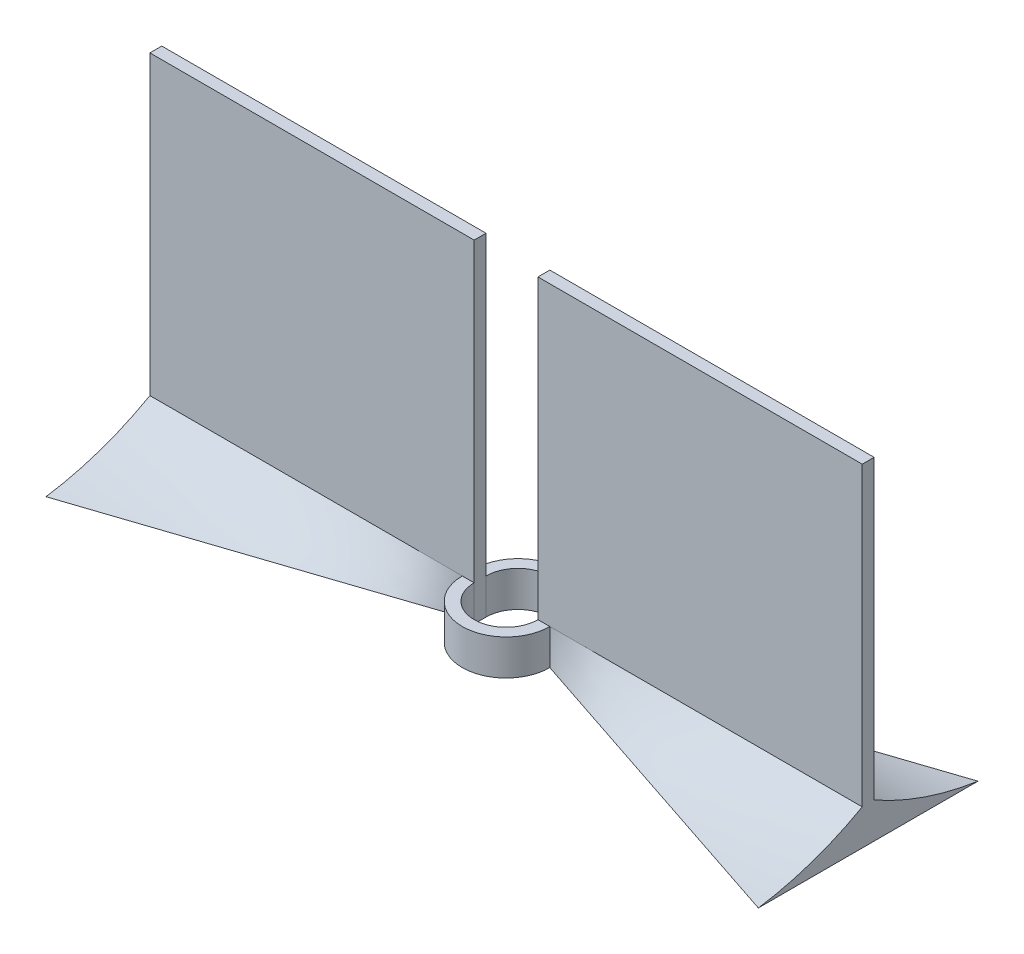
SolidWorks part; units mm, degrees
ref_plane "Front Plane" through (0, 0, 0) normal (0, 0, 1) x (1, 0, 0)
ref_plane "Top Plane" through (0, 0, 0) normal (0, 1, 0) x (1, 0, 0)
ref_plane "Right Plane" through (0, 0, 0) normal (1, 0, 0) x (0, 0, -1)
ref_plane "Plane1" through (10.75, 0, 0) normal (1, 0, 0) x (0, 0, -1)
ref_plane "Plane2" through (120, 0, 0) normal (1, 0, 0) x (0, 0, -1)
sketch "Sketch1" plane through (10.75, 0, 0) normal (1, 0, 0) x (0, 0, -1)
  line L0 (0, 0) -> (0, 12)
  line L1 (0, 55) -> (0, -55) construction
  line L2 (0, 12) -> (0, 112)
  line L3 (0, 112) -> (2, 112)
  line L4 (0, 112) -> (-2, 112)
  line L6 (2, 112) -> (-2, 112)
  line L7 (2, 112) -> (2, 12)
  line L8 (2, 12) -> (-2, 12)
  line L9 (-2, 112) -> (-2, 12)
  line L10 (2, 12) -> (-2, 12)
  line L11 (2, 12) -> (2, 0)
  line L12 (2, 0) -> (-2, 0)
  line L13 (-2, 12) -> (-2, 0)
  dimension "D1" = 100
  dimension "D2" = 4
  dimension "D3" = 12
extrude "Boss-Extrude1" add sketch "Sketch1" along normal blind 109.25 contours L7 L6 L9 L8
sketch "Sketch5" plane through (120, 0, 0) normal (1, 0, 0) x (0, 0, -1)
  line L1 (-2, 12) -> (2, 12)
  line L6 (-37, 0) -> (37, 0)
  spline S0 degree 2 poles (-2, 12) (-18.4033, 2.78) (-37, 0) knots 0 0 0 1 1 1
  spline S1 degree 2 poles (2, 12) (18.4033, 2.78) (37, 0) knots 0 0 0 1 1 1
  dimension "D1" = 74
  dimension "D2" = 4
sketch "Sketch6" plane through (10.75, 0, 0) normal (-1, 0, 0) x (0, 0, 1)
  line L3 (-2, 12) -> (2, 12)
  line L4 (-2, 12) -> (-2, 0)
  line L5 (-2, 0) -> (2, 0)
  line L6 (2, 12) -> (2, 0)
  dimension "D1" = 12
ref_plane "Plane3" through (14.75, 0, 0) normal (1, 0, 0) x (0, 0, -1)
sketch "Sketch7" plane through (14.75, 0, 0) normal (1, 0, 0) x (0, 0, -1)
  line L1 (-2, 12) -> (2, 12)
  line L2 (-2, 12) -> (-2, 0)
  line L3 (-2, 0) -> (2, 0)
  line L4 (2, 12) -> (2, 0)
  point P6 (0, 0)
extrude "Boss-Extrude2" add sketch "Sketch6" against normal up to vertex (4 mm away) contours L6 L5 L4 L3 up to point (14.75, 0, -2)
loft "Loft3" add profiles "Sketch7", "Sketch5" connector at (14.75, 0, -2) connector at (120, 0, -37)
sketch "Sketch8" plane through (0, 0, 2) normal (0, 0, 1) x (1, 0, 0)
  line L1 (14.75, 12) -> (10.75, 12)
  line L2 (14.75, 12) -> (14.75, 0)
  line L3 (14.75, 0) -> (10.75, 0)
  line L4 (10.75, 12) -> (10.75, 0)
sketch "Sketch9" plane through (0, 0, 0) normal (1, 0, 0) x (0, 0, -1)
  line L0 (0, -2.1666) -> (0, 77.6532)
  line L1 (0, 60.0876) -> (0, -60.0876) construction
sketch "Sketch10" plane through (0, 0, 0) normal (1, 0, 0) x (0, 0, -1)
  line L0 (0, 3.6076) -> (-2, 3.6076)
  line L1 (0, -2.1666) -> (0, 77.6532) construction
  line L2 (-2, 12) -> (-2, 0) construction
  line L3 (-2, 3.6076) -> (-2, 71.7092)
  line L4 (-2, 112) -> (-2, 0) construction
sketch "Sketch11" plane through (0, 0, 0) normal (1, 0, 0) x (0, 0, -1)
  line L0 (0, 3.6076) -> (2, 3.6076)
  line L1 (2, 12) -> (2, 0) construction
  line L2 (2, 3.6076) -> (2, 29.9017)
  line L3 (2, 112) -> (2, 0) construction
sketch "Sketch12" plane through (0, 0, -2) normal (0, 0, -1) x (-1, 0, 0)
  line L1 (-14.75, 12) -> (-10.75, 12)
  line L2 (-14.75, 12) -> (-14.75, 0)
  line L3 (-14.75, 0) -> (-10.75, 0)
  line L4 (-10.75, 12) -> (-10.75, 0)
revolve "Revolve3" add sketch "Sketch8" angle 180 about L3 reverse direction yes
revolve "Revolve4" add sketch "Sketch12" angle 180 about L2
mirror "Mirror3" about plane through (0, 0, 0) normal (1, 0, 0) of bodies 105
